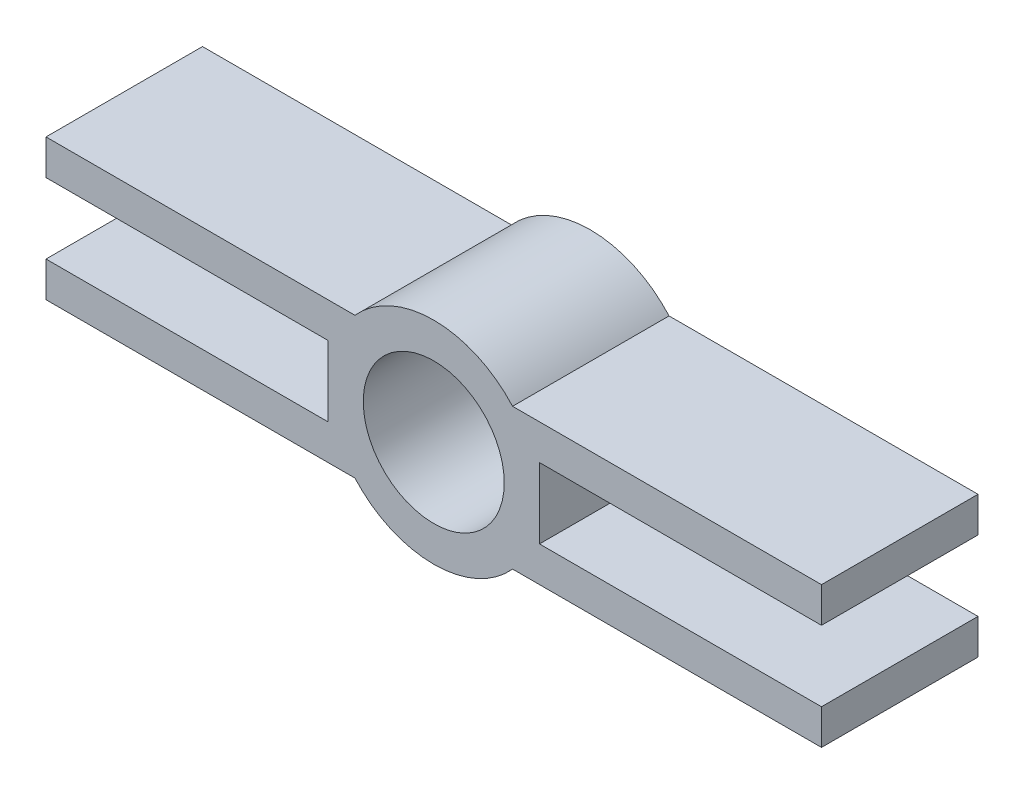
SolidWorks part; units mm, degrees
ref_plane "Front Plane" through (0, 0, 0) normal (0, 0, 1) x (1, 0, 0)
ref_plane "Top Plane" through (0, 0, 0) normal (0, 1, 0) x (1, 0, 0)
ref_plane "Right Plane" through (0, 0, 0) normal (1, 0, 0) x (0, 0, -1)
sketch "Sketch1" plane through (0, 0, 0) normal (0, 0, 1) x (1, 0, 0)
  line L0 (4.851, 0) -> (-50.8, 0)
  line L1 (-50.8, 0) -> (-50.8, 6.35)
  line L2 (-50.8, 6.35) -> (0, 6.35)
  line L3 (0, 6.35) -> (0, 19.05)
  line L4 (0, 19.05) -> (-50.8, 19.05)
  line L5 (-50.8, 19.05) -> (-50.8, 25.4)
  line L6 (-50.8, 25.4) -> (4.851, 25.4)
  line L7 (-50.8, 19.05) -> (-97.7976, 19.05) construction
  line L8 (-97.7976, 19.05) -> (-97.7976, 6.35) construction
  line L9 (-97.7976, 6.35) -> (-50.8, 6.35) construction
  line L10 (0, 12.7) -> (6.35, 12.7) construction
  line L11 (6.35, 12.7) -> (6.35, 4.7841) construction
  line L12 (31.75, 12.7) -> (31.75, 4.7841) construction
  line L13 (19.05, 25.4) -> (19.05, -5.9402) construction
  line L14 (88.9, 0) -> (88.9, 6.35)
  line L15 (88.9, 19.05) -> (88.9, 25.4)
  line L16 (38.1, 12.7) -> (31.75, 12.7) construction
  line L17 (88.9, 25.4) -> (33.249, 25.4)
  line L18 (38.1, 19.05) -> (88.9, 19.05)
  line L19 (38.1, 6.35) -> (38.1, 19.05)
  line L20 (88.9, 6.35) -> (38.1, 6.35)
  line L21 (33.249, 0) -> (88.9, 0)
  circle A0 centre (19.05, 12.7) radius 12.7
  arc A1 (4.851, 0) -> (33.249, 0) centre (19.05, 12.7) ccw
  arc A2 (33.249, 25.4) -> (4.851, 25.4) centre (19.05, 12.7) ccw
  point P0 (0, 0)
  dimension "D1" = 25.4
  dimension "D2" = 6.35
  dimension "D3" = 12.7
  dimension "D4" = 6.35
  dimension "D5" = 50.8
extrude "Boss-Extrude1" add sketch "Sketch1" along normal blind 28.194
